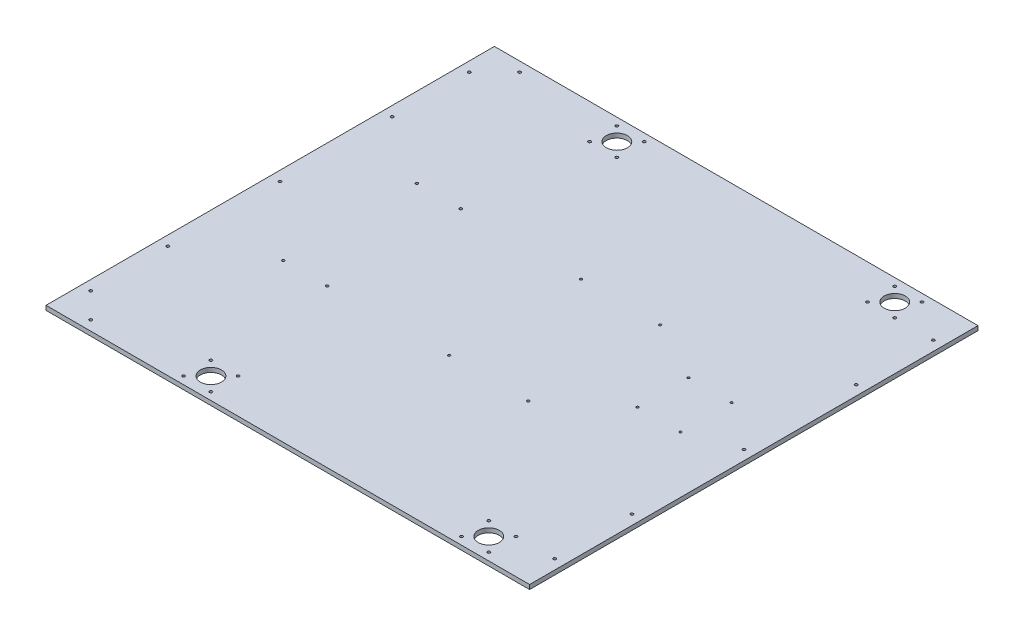
SolidWorks part; units mm, degrees
ref_plane "Front Plane" through (0, 0, 0) normal (0, 0, 1) x (1, 0, 0)
ref_plane "Top Plane" through (0, 0, 0) normal (0, 1, 0) x (1, 0, 0)
ref_plane "Right Plane" through (0, 0, 0) normal (1, 0, 0) x (0, 0, -1)
sketch "Sketch1" plane through (0, 0, 0) normal (1, 0, 0) x (0, 0, -1)
  line L0 (0, 0) -> (-510, 0)
  line L1 (-510, 0) -> (-510, 5)
  line L2 (-510, 5) -> (0, 5)
  line L6 (0, 5) -> (0, 0)
  point P2 (0, 0)
  dimension "D1" = 510
  dimension "D2" = 5
extrude "Boss-Extrude1" add sketch "Sketch1" along normal blind 550
sketch "BotthomHoles-Sketch2" plane through (0, 5, 0) normal (0, 1, 0) x (1, 0, 0)
  line L0 (550, -3.175) -> (0, -3.175) construction
  line L2 (550, 0) -> (550, -510) construction
  line L3 (550, 0) -> (0, 0) construction
  line L4 (550, -510) -> (0, -510) construction
  line L7 (0, 0) -> (0, -510) construction
  line L8 (550, 0) -> (550, -510) construction
  circle A0 centre (479.425, -24.175) radius 12
  circle A2 centre (463.925, -8.675) radius 1.5875
  circle A3 centre (494.925, -8.675) radius 1.5875
  circle A6 centre (463.925, -39.675) radius 1.5875
  circle A7 centre (494.925, -39.675) radius 1.5875
  circle A8 centre (39.6875, -11.1125) radius 1.5875
  circle A10 centre (178.925, -39.675) radius 1.5875
  circle A11 centre (147.925, -39.675) radius 1.5875
  circle A12 centre (178.925, -8.675) radius 1.5875
  circle A13 centre (147.925, -8.675) radius 1.5875
  circle A14 centre (163.425, -24.175) radius 12
  circle A15 centre (39.6875, -498.8875) radius 1.5875
  circle A16 centre (147.925, -501.325) radius 1.5875
  circle A17 centre (178.925, -501.325) radius 1.5875
  circle A18 centre (147.925, -470.325) radius 1.5875
  circle A19 centre (178.925, -470.325) radius 1.5875
  circle A20 centre (463.925, -470.325) radius 1.5875
  circle A21 centre (463.925, -501.325) radius 1.5875
  circle A22 centre (494.925, -470.325) radius 1.5875
  circle A23 centre (494.925, -501.325) radius 1.5875
  circle A25 centre (163.425, -485.825) radius 12
  circle A26 centre (479.425, -485.825) radius 12
  circle A27 centre (11.1125, -39.6875) radius 1.5875
  circle A28 centre (11.1125, -127.5) radius 1.5875
  circle A29 centre (11.1125, -255) radius 1.5875
  circle A30 centre (11.1125, -382.5) radius 1.5875
  circle A31 centre (11.1125, -470.3125) radius 1.5875
  circle A32 centre (538.8875, -470.3125) radius 1.5875
  circle A33 centre (538.8875, -382.5) radius 1.5875
  circle A34 centre (538.8875, -255) radius 1.5875
  circle A35 centre (538.8875, -127.5) radius 1.5875
  circle A36 centre (538.8875, -39.6875) radius 1.5875
  dimension "D9" = 3.175
  dimension "D10" = 24
  dimension "D13" = 3.175
  dimension "D29" = 3.175
  dimension "D2" = 8.675
  dimension "D5" = 15.5
  dimension "D6" = 31
  dimension "D7" = 15.5
  dimension "D8" = 31
  dimension "D11" = 21
  dimension "D12" = 39.6875
  dimension "D15" = 31
  dimension "D16" = 15.5
  dimension "D17" = 316
  dimension "D3" = 70.575
  dimension "D4" = 11.1125
  dimension "D18" = 8.675
  dimension "D19" = 15.5
  dimension "D20" = 31
  dimension "D21" = 11.1125
  dimension "D22" = 39.6875
  dimension "D23" = 39.6875
  dimension "D24" = 127.5
  dimension "D25" = 127.5
  dimension "D26" = 127.5
  dimension "D27" = 11.1125
  dimension "D28" = 11.1125
extrude "BottomHoles-Cut-Extrude1" cut sketch "BotthomHoles-Sketch2" against normal through all
sketch "BottomPSUHolesSketch2" plane through (0, 5, 0) normal (0, 1, 0) x (1, 0, 0)
  line L0 (0, 0) -> (0, -510) construction
  line L1 (550, 0) -> (0, 0) construction
  line L2 (550, -510) -> (0, -510) construction
  circle A0 centre (90.8, -179) radius 1.5
  circle A1 centre (140.8, -179) radius 1.5
  circle A2 centre (90.8, -331) radius 1.5
  circle A3 centre (140.8, -331) radius 1.5
  dimension "D6" = 3
  dimension "D1" = 152
  dimension "D2" = 50
  dimension "D3" = 90.8
  dimension "D4" = 179
  dimension "D5" = 179
extrude "BottomPSUHolesCut-Extrude1" cut sketch "BottomPSUHolesSketch2" against normal through all
sketch "BottomMainboardHolesSketch2" plane through (0, 5, 0) normal (0, 1, 0) x (1, 0, 0)
  line L0 (550, 0) -> (0, 0) construction
  line L1 (0, 0) -> (0, -510) construction
  line L2 (550, 0) -> (550, -510) construction
  line L3 (550, -510) -> (0, -510) construction
  circle A0 centre (278.5, -180) radius 1.35
  circle A1 centre (368.5, -180) radius 1.35
  circle A2 centre (278.5, -330) radius 1.35
  circle A3 centre (368.5, -330) radius 1.35
  circle A4 centre (436.7, -216) radius 1.35
  circle A5 centre (485.7, -216) radius 1.35
  circle A6 centre (436.7, -274) radius 1.35
  circle A7 centre (485.7, -274) radius 1.35
  dimension "D6" = 2.7
  dimension "D7" = 2.7
  dimension "D1" = 90
  dimension "D2" = 150
  dimension "D3" = 180
  dimension "D4" = 58
  dimension "D5" = 49
  dimension "D8" = 216
  dimension "D9" = 278.5
  dimension "D10" = 64.3
  dimension "D11" = 236
extrude "BottomMainboardHolesCut-Extrude1" cut sketch "BottomMainboardHolesSketch2" against normal through all
equation "\"LowerRailWidth\"= 2.00in"
equation "\"RailThickness\"= .125in'Spec"
equation "\"StepperHoleDiameter\"= 24mm"
equation "\"StepperMountingHoleDiameter\"= 3.175mm"
equation "\"SideRailLength\"= 550mm"
equation "\"StepperMountingHoleDistance\"= 31mm'Spec"
equation "\"StepperMountingHoleOffsetFromLeftOrRightSide\"= \"StepperMountingHoleOffsetFromItsSide\" + \"RailThickness\""
equation "\"HoleOffsetFromEdge\"= \"RailThickness\" * 2.5"
equation "\"HoleOffsetFromSide\"= \"RailThickness\" * 3.5"
equation "\"StepperMountingHoleOffsetFromItsSide\"= 5.5mm'Spec"
equation "\"FasteningHoleDiameter\"= .125in"
equation "\"D2@BotthomHoles-Sketch2\" = \"StepperMountingHoleOffsetFromLeftOrRightSide\""
equation "\"D5@BotthomHoles-Sketch2\" = \"StepperMountingHoleDistance\" / 2"
equation "\"D6@BotthomHoles-Sketch2\" = \"StepperMountingHoleDistance\""
equation "\"D7@BotthomHoles-Sketch2\" = \"StepperMountingHoleDistance\" / 2"
equation "\"D8@BotthomHoles-Sketch2\" = \"StepperMountingHoleDistance\""
equation "\"D9@BotthomHoles-Sketch2\" = \"StepperMountingHoleDiameter\""
equation "\"D10@BotthomHoles-Sketch2\" = \"StepperHoleDiameter\""
equation "\"D1@Boss-Extrude1\"=\"SideRailLength\""
equation "\"BedOverlap\"= 20mm"
equation "\"BedThirdSize\"= 70mm"
equation "\"BedInnerSquareWidth\"= \"BedThirdSize\" * 3'Equals 210"
equation "\"BedInnerSquareLength\"= \"BedInnerSquareWidth\""
equation "\"BedLWidth\"= \"BedThirdSize\" + \"BedOverlap\"'Equals 90"
equation "\"BedLength\"= \"BedInnerSquareLength\" + \"BedLWidth\" * 2 - \"BedOverlap\" * 2 + \"BedIncreasedByLength\"'Equals 350"
equation "\"DistanceBetweenFrontToBackStepperHoles\"= \"BedLength\" - \"DistanceFromBedFrontToFirstLeftStepperHole\"'Equals 316"
equation "\"DistanceFromBedFrontToFirstLeftStepperHole\"= \"LeadScrewNutPadSize\" + 10mm'Equals 34"
equation "\"DistanceFromFrontSideToBedFront\"= \"RailThickness\" + \"BeltTensionerDepth\" + 10mm'Equals 36.575"
equation "\"20TGT2PulleyDiameter\"= 17.9mm'Spec"
equation "\"BeltTensionerBackWallThickness\"= 4mm"
equation "\"BeltTensionerSpaceBetweenPulleyAndWall\"= 1.5mm"
equation "\"BeltTensionerInnerDepth\"= \"20TGT2PulleyDiameter\" + \"BeltTensionerSpaceBetweenPulleyAndWall\""
equation "\"BeltTensionerDepth\"= \"BeltTensionerBackWallThickness\" + \"BeltTensionerInnerDepth\"'Equals 23.4"
equation "\"BedIncreasedByLength\"= 0mm"
equation "\"LowerCornerBlockWidth\"= \"LowerRailWidth\" - \"RailThickness\" * 2'Room for left front stepper"
equation "\"D12@BotthomHoles-Sketch2\"=\"CornerEnclosureOffset\""
equation "\"D13@BotthomHoles-Sketch2\"=\"FasteningHoleDiameter\""
equation "\"CornerEnclosureOffset\"= \"LowerCornerBlockWidth\" - \"HoleOffsetFromEdge\" + \"RailThickness\""
equation "\"LowerCornerBlockY1FromSide\"= \"HoleOffsetFromSide\""
equation "\"D15@BotthomHoles-Sketch2\"=\"StepperMountingHoleDistance\""
equation "\"D16@BotthomHoles-Sketch2\"=\"StepperMountingHoleDistance\"/2"
equation "\"D17@BotthomHoles-Sketch2\"=\"DistanceBetweenFrontToBackStepperHoles\""
equation "\"DistanceFromFrontSideToFirstLeftStepperHole\"= \"DistanceFromFrontSideToBedFront\" + \"DistanceFromBedFrontToFirstLeftStepperHole\"'Equals 70.575"
equation "\"LeadScrewNutMountingHoleFlangeDiameter\"= 22mm'Spec"
equation "\"LeadScrewNutPadSize\"= \"LeadScrewNutMountingHoleFlangeDiameter\" + 2mm'Equals 24"
equation "\"D3@BotthomHoles-Sketch2\"=\"DistanceFromFrontSideToFirstLeftStepperHole\""
equation "\"LowerEnclosureThickness\"= 5mm"
equation "\"FrontBackRailLength\"= 510mm"
equation "\"D4@BotthomHoles-Sketch2\"=\"LowerCornerBlockY1FromSide\""
equation "\"D1@Sketch1\"=\"FrontBackRailLength\""
equation "\"D18@BotthomHoles-Sketch2\"=\"StepperMountingHoleOffsetFromLeftOrRightSide\""
equation "\"D19@BotthomHoles-Sketch2\"=\"StepperMountingHoleDistance\"/2"
equation "\"D20@BotthomHoles-Sketch2\"=\"StepperMountingHoleDistance\""
equation "\"D21@BotthomHoles-Sketch2\"=\"LowerCornerBlockY1FromSide\""
equation "\"D22@BotthomHoles-Sketch2\"=\"CornerEnclosureOffset\""
equation "\"D23@BotthomHoles-Sketch2\"=\"CornerEnclosureOffset\""
equation "\"FrontOrBackEnclosureOffsets\"= \"FrontBackRailLength\" / 4"
equation "\"D24@BotthomHoles-Sketch2\"=\"FrontOrBackEnclosureOffsets\""
equation "\"D25@BotthomHoles-Sketch2\"=\"FrontOrBackEnclosureOffsets\""
equation "\"D26@BotthomHoles-Sketch2\"=\"FrontOrBackEnclosureOffsets\""
equation "\"D27@BotthomHoles-Sketch2\"=\"LowerCornerBlockY1FromSide\""
equation "\"D28@BotthomHoles-Sketch2\"=\"LowerCornerBlockY1FromSide\""
equation "\"D29@BotthomHoles-Sketch2\"=\"FasteningHoleDiameter\""
equation "\"D2@Sketch1\"=\"LowerEnclosureThickness\""
equation "\"24VPSUMountingHolesShortDistanceBetween\"= 50mm'Yours may differ"
equation "\"24VPSUMountingHolesLongDistanceBetween\"= 152mm'Yours may differ"
equation "\"24VPSUMountingHoleOffsetFromEitherSide\"= 30mm'Yours may differ"
equation "\"24VPSUMountingHoleOffsetFromEdge\"= \"24VPSUMountingHoleOffsetFromEitherSide\" + \"LowerRailWidth\" + 10mm'Yours may differ"
equation "\"24VPSUMountingHoleDiameter\"= 3mm'Yours may differ"
equation "\"D2@BottomPSUHolesSketch2\" = \"24VPSUMountingHolesShortDistanceBetween\""
equation "\"D1@BottomPSUHolesSketch2\" = \"24VPSUMountingHolesLongDistanceBetween\""
equation "\"D3@BottomPSUHolesSketch2\" = \"24VPSUMountingHoleOffsetFromEdge\""
equation "\"D4@BottomPSUHolesSketch2\" =  ( \"FrontBackRailLength\" - \"24VPSUMountingHolesLongDistanceBetween\" )  / 2"
equation "\"D6@BottomPSUHolesSketch2\" = \"24VPSUMountingHoleDiameter\""
equation "\"RPi4BoardLength\"= 85mm'Spec"
equation "\"RPi4BoardWidth\"= 56mm'Spec"
equation "\"RPi4BoardMountingHoleOffsetFromEdge\"= 3.5mm'Spec"
equation "\"RPi4BoardMountingHoleDiameter\"= 2.7mm'Spec"
equation "\"OctopusV1.1BoardLength\"= 160mm'Spec"
equation "\"OctopusV1.1BoardWidth\"= 100mm'Spec"
equation "\"OctopusV1.1BoardMountingHoleOffsetFromAllEdges\"= 3.5mm'Spec"
equation "\"OctopusV1.1BoardMountingHoleLengthDistanceBetween\"= 150mm'Spec"
equation "\"OctopusV1.1BoardMountingHoleWidthDistanceBetween\"= 90mm'Spec"
equation "\"D2@BottomMainboardHolesSketch2\" = \"OctopusV1.1BoardMountingHoleLengthDistanceBetween\""
equation "\"D3@BottomMainboardHolesSketch2\" =  ( \"FrontBackRailLength\" - \"OctopusV1.1BoardMountingHoleLengthDistanceBetween\" )  / 2"
equation "\"D4@BottomMainboardHolesSketch2\" = \"RPi4BoardMountingHoleLengthDistanceBetween\""
equation "\"D5@BottomMainboardHolesSketch2\"=\"RPi4BoardWidth\"- \"RPi4BoardMountingHoleOffsetFromEdge\" * 2"
equation "\"D6@BottomMainboardHolesSketch2\" = \"OctopusV1.1BoardMountingHoleDiameter\""
equation "\"D7@BottomMainboardHolesSketch2\" = \"RPi4BoardMountingHoleDiameter\""
equation "\"RPi4BoardMountingHoleLengthDistanceBetween\"= 58mm'Spec"
equation "\"OctopusV1.1BoardMountingHoleDiameter\"= 2.7mm'Spec"
equation "\"D1@BottomMainboardHolesSketch2\" = \"OctopusV1.1BoardMountingHoleWidthDistanceBetween\""
equation "\"D8@BottomMainboardHolesSketch2\" =  ( \"FrontBackRailLength\" - \"RPi4BoardLength\" )  / 2 + \"RPi4BoardMountingHoleOffsetFromEdge\""
equation "\"D9@BottomMainboardHolesSketch2\" = \"SideRailLength\" / 2 + \"OctopusV1.1BoardMountingHoleOffsetFromAllEdges\""
equation "\"D10@BottomMainboardHolesSketch2\" = \"LowerRailWidth\" + \"RPi4BoardMountingHoleOffsetFromEdge\" + 10mm"
